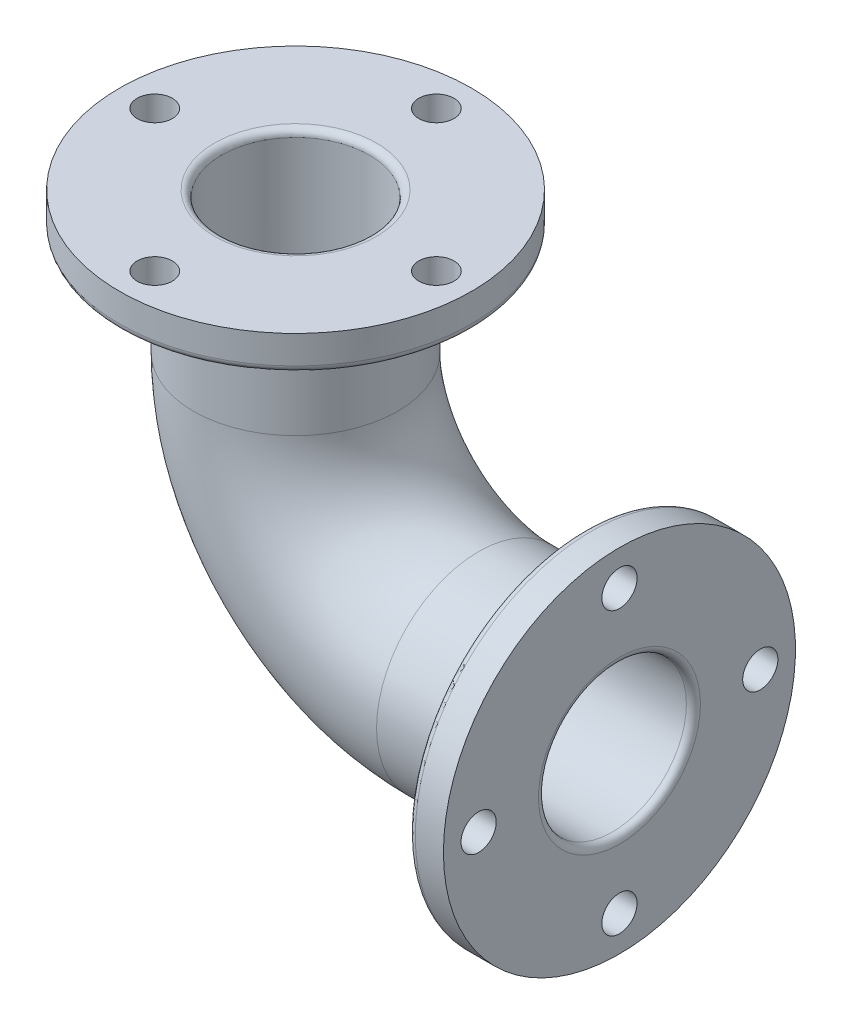
SolidWorks part; units mm, degrees
ref_plane "Front Plane" through (0, 0, 0) normal (0, 0, 1) x (1, 0, 0)
ref_plane "Top Plane" through (0, 0, 0) normal (0, 1, 0) x (1, 0, 0)
ref_plane "Right Plane" through (0, 0, 0) normal (1, 0, 0) x (0, 0, -1)
sketch "Sketch2" plane through (0, 0, 0) normal (0, 0, 1) x (1, 0, 0)
  line L0 (0, 3810) -> (0, 0)
  line L1 (6604, -6604) -> (10414, -6604)
  arc A0 (0, 0) -> (6604, -6604) centre (6604, 0) ccw
  dimension "D3" = 6604
  dimension "D1" = 3810
  dimension "D2" = 3810
sweep "Sweep-Thin1" add path "Sketch2" circular profile diameter 7366 parameters "D1"=1016, "D3"=7366
sketch "Sketch40" plane through (10414, 0, 0) normal (1, 0, 0) x (0, 0, -1)
  circle A0 centre (0, -6604) radius 2667 construction
  circle A1 centre (0, -6604) radius 2667
  circle A2 centre (0, -6604) radius 6350
  dimension "D1" = 12700
extrude "Boss-Extrude1" add sketch "Sketch40" along normal blind 1270 contours A2 | A1
sketch "Sketch41" plane through (0, 3810, 0) normal (0, 1, 0) x (1, 0, 0)
  circle A0 centre (0, 0) radius 2667 construction
  circle A1 centre (0, 0) radius 2667
  circle A2 centre (0, 0) radius 6350
  dimension "D1" = 12700
extrude "Boss-Extrude2" add sketch "Sketch41" along normal blind 1270 contours A2 | A1
sketch "Sketch42" plane through (0, 5080, 0) normal (0, 1, 0) x (1, 0, 0)
  circle A0 centre (0, 0) radius 5080 construction
  circle A1 centre (0, 5080) radius 635
  circle A2 centre (5080, 0) radius 635
  circle A3 centre (0, -5080) radius 635
  circle A4 centre (-5080, 0) radius 635
  dimension "D1" = 10160
  dimension "D2" = 1270
  dimension "D3" = 4
extrude "Cut-Extrude1" cut sketch "Sketch42" against normal blind 1270
sketch "Sketch43" plane through (11684, 0, 0) normal (1, 0, 0) x (0, 0, -1)
  circle A0 centre (0, -6604) radius 5080 construction
  circle A1 centre (0, -1524) radius 635
  circle A2 centre (5080, -6604) radius 635
  circle A3 centre (0, -11684) radius 635
  circle A4 centre (-5080, -6604) radius 635
  dimension "D1" = 10160
  dimension "D2" = 1270
  dimension "D3" = 4
extrude "Cut-Extrude2" cut sketch "Sketch43" against normal blind 1270
fillet "Fillet1" radius 254 6 edges at (0, 3810, 3683) (10414, -6604, 3683) (0, 5080, 2667) (11684, -6604, -2667) (10414, -6604, -6350) (0, 3810, 6350)
